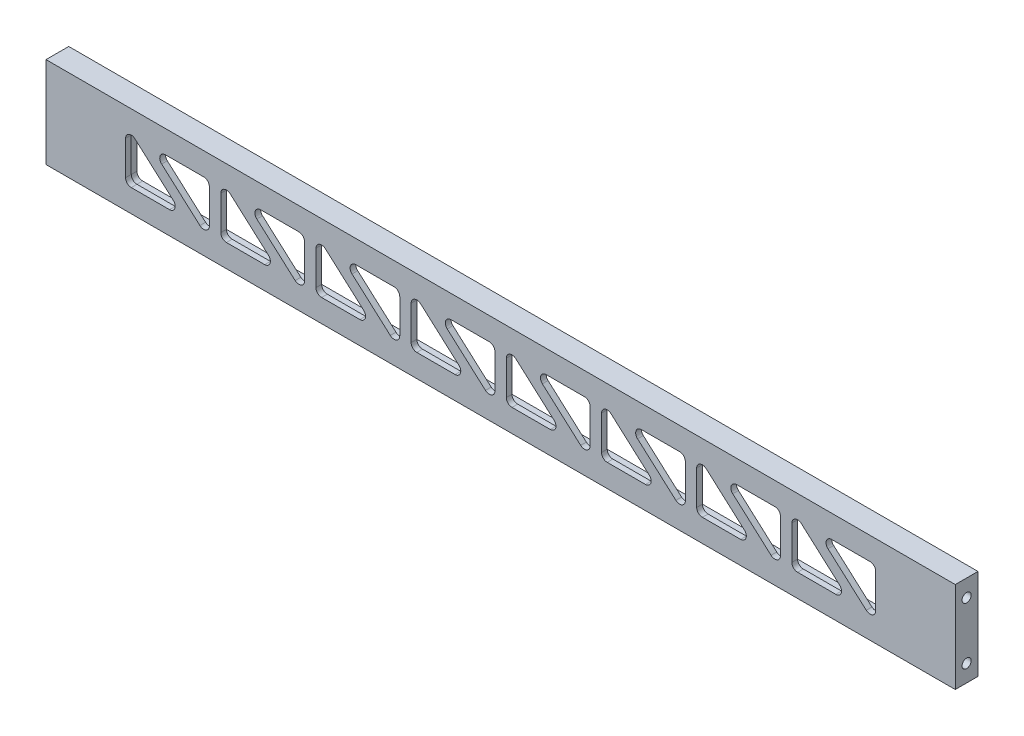
SolidWorks part; units mm, degrees
material "6061 Alloy"
ref_plane "Front Plane" through (0, 0, 0) normal (0, 0, 1) x (1, 0, 0)
ref_plane "Top Plane" through (0, 0, 0) normal (0, 1, 0) x (1, 0, 0)
ref_plane "Right Plane" through (0, 0, 0) normal (1, 0, 0) x (0, 0, -1)
sketch "Sketch1" plane through (0, 0, 0) normal (1, 0, 0) x (0, 0, -1)
  line L1 (0, 0) -> (12.7, 0)
  line L2 (0, 0) -> (0, 50.8)
  line L3 (0, 50.8) -> (12.7, 50.8)
  line L4 (12.7, 0) -> (12.7, 50.8)
  dimension "D1" = 12.7
  dimension "D2" = 50.8
extrude "Boss-Extrude1" add sketch "Sketch1" along normal mid plane 508
hole_wizard "1/4-20 Tapped Hole1" positions "3DSketch1" profile "Sketch2" tap size "1/4-20" standard "ANSI Inch"
sketch3d "3DSketch1"
  line L2 (254, 9.525, -6.35) -> (254, 41.275, -6.35) construction
  line L4 (254, 41.275, -6.35) -> (254, 50.8, -6.35) construction
  line L5 (254, 50.8, -12.7) -> (254, 50.8, 0) construction
  line L8 (254, 9.525, -6.35) -> (254, 0, -6.35) construction
  line L9 (254, 0, 0) -> (254, 0, -12.7) construction
  point P0 (254, 41.275, -6.35)
  point P2 (254, 9.525, -6.35)
  point P4 (-254, 9.525, -6.35)
  point P6 (-254, 41.275, -6.35)
  dimension "D1" = 31.75
sketch "Sketch2" plane through (254, 41.275, -6.35) normal (0, 1, 0) x (0, 0, -1)
  line L0 (0, 0) -> (0, 30.7438)
  line L1 (0, 30.7438) -> (2.5527, 29.21)
  line L2 (2.5527, 29.21) -> (2.5527, 0)
  line L5 (2.5527, 0) -> (0, 0)
  line L10 (0, 30.7438) -> (-2.5527, 29.21) construction
  line L11 (0, -6.35) -> (0, 107.95) construction
  dimension "Tap Drill Dia." = 5.1054
  dimension "Tap Drill Depth" = 29.21
  dimension "Drill Angle" = 118
sketch "Sketch4" plane through (0, 0, -12.7) normal (0, 0, -1) x (-1, 0, 0)
  line L0 (0, 0) -> (0, 6.35) construction
  line L1 (212.725, 44.45) -> (-212.725, 44.45)
  line L2 (215.9, 41.275) -> (215.9, 9.525)
  line L3 (212.725, 6.35) -> (-212.725, 6.35)
  line L4 (-215.9, 41.275) -> (-215.9, 9.525)
  line L5 (-254, 0) -> (254, 0) construction
  line L6 (0, 44.45) -> (0, 50.8) construction
  line L7 (-254, 50.8) -> (254, 50.8) construction
  line L8 (254, 25.4) -> (215.9, 25.4) construction
  line L9 (254, 0) -> (254, 50.8) construction
  line L10 (-254, 25.4) -> (-215.9, 25.4) construction
  line L11 (-254, 0) -> (-254, 50.8) construction
  arc A0 (-212.725, 6.35) -> (-215.9, 9.525) centre (-212.725, 9.525) cw
  arc A1 (-212.725, 44.45) -> (-215.9, 41.275) centre (-212.725, 41.275) ccw
  arc A2 (215.9, 9.525) -> (212.725, 6.35) centre (212.725, 9.525) cw
  arc A3 (212.725, 44.45) -> (215.9, 41.275) centre (212.725, 41.275) cw
  dimension "D1" = 3.175
  dimension "D2" = 6.35
  dimension "D3" = 38.1
extrude "Cut-Extrude1" cut sketch "Sketch4" against normal blind 9.525
sketch "Sketch5" plane through (0, 0, -3.175) normal (0, 0, -1) x (-1, 0, 0)
  line L0 (-209.55, 34.925) -> (-209.55, 15.875)
  line L1 (-204.2632, 13.5041) -> (-182.876, 32.5541)
  line L2 (-184.9878, 38.1) -> (-206.375, 38.1)
  line L3 (-189.3927, 18.2459) -> (-168.0055, 37.2959)
  line L4 (-162.7188, 34.925) -> (-162.7188, 15.875)
  line L5 (-165.8937, 12.7) -> (-187.2809, 12.7)
  line L6 (212.725, 44.45) -> (-212.725, 44.45) construction
  line L7 (-212.725, 6.35) -> (212.725, 6.35) construction
  line L8 (-215.9, 25.4) -> (-209.55, 25.4) construction
  line L9 (-215.9, 41.275) -> (-215.9, 9.525) construction
  line L10 (-193.5696, 23.0291) -> (-189.3461, 18.2874) construction
  line L11 (-162.7187, 25.4) -> (-156.3687, 25.4) construction
  line L12 (-156.3687, 34.925) -> (-156.3687, 15.875)
  line L13 (-131.8066, 38.1) -> (-153.1937, 38.1)
  line L14 (-151.082, 13.5041) -> (-129.6948, 32.5541)
  line L15 (-140.3884, 23.0291) -> (-136.1648, 18.2874) construction
  line L16 (-136.2115, 18.2459) -> (-114.8243, 37.2959)
  line L17 (-109.5375, 34.925) -> (-109.5375, 15.875)
  line L18 (-112.7125, 12.7) -> (-134.0997, 12.7)
  line L19 (-109.5375, 25.4) -> (-103.1875, 25.4) construction
  line L20 (-103.1875, 34.925) -> (-103.1875, 15.875)
  line L21 (-78.6253, 38.1) -> (-100.0125, 38.1)
  line L22 (-97.9007, 13.5041) -> (-76.5135, 32.5541)
  line L23 (-87.2071, 23.0291) -> (-82.9836, 18.2874) construction
  line L24 (-83.0302, 18.2459) -> (-61.643, 37.2959)
  line L25 (-56.3563, 34.925) -> (-56.3563, 15.875)
  line L26 (-59.5313, 12.7) -> (-80.9184, 12.7)
  line L27 (-56.3562, 25.4) -> (-50.0062, 25.4) construction
  line L28 (-50.0063, 34.925) -> (-50.0063, 15.875)
  line L29 (-25.4441, 38.1) -> (-46.8313, 38.1)
  line L30 (-44.7195, 13.5041) -> (-23.3323, 32.5541)
  line L31 (-34.0259, 23.0291) -> (-29.8023, 18.2874) construction
  line L32 (-29.849, 18.2459) -> (-8.4618, 37.2959)
  line L33 (-3.175, 34.925) -> (-3.175, 15.875)
  line L34 (-6.35, 12.7) -> (-27.7372, 12.7)
  line L35 (-3.175, 25.4) -> (3.175, 25.4) construction
  line L36 (3.175, 34.925) -> (3.175, 15.875)
  line L37 (27.7372, 38.1) -> (6.35, 38.1)
  line L38 (8.4618, 13.5041) -> (29.849, 32.5541)
  line L39 (19.1554, 23.0291) -> (23.3789, 18.2874) construction
  line L40 (23.3323, 18.2459) -> (44.7195, 37.2959)
  line L41 (50.0062, 34.925) -> (50.0062, 15.875)
  line L42 (46.8312, 12.7) -> (25.4441, 12.7)
  line L43 (50.0062, 25.4) -> (56.3562, 25.4) construction
  line L44 (56.3562, 34.925) -> (56.3562, 15.875)
  line L45 (80.9184, 38.1) -> (59.5312, 38.1)
  line L46 (61.643, 13.5041) -> (83.0302, 32.5541)
  line L47 (72.3366, 23.0291) -> (76.5602, 18.2874) construction
  line L48 (76.5135, 18.2459) -> (97.9007, 37.2959)
  line L49 (103.1875, 34.925) -> (103.1875, 15.875)
  line L50 (100.0125, 12.7) -> (78.6253, 12.7)
  line L51 (103.1875, 25.4) -> (109.5375, 25.4) construction
  line L52 (109.5375, 34.925) -> (109.5375, 15.875)
  line L53 (134.0997, 38.1) -> (112.7125, 38.1)
  line L54 (114.8243, 13.5041) -> (136.2115, 32.5541)
  line L55 (125.5179, 23.0291) -> (129.7414, 18.2874) construction
  line L56 (129.6948, 18.2459) -> (151.082, 37.2959)
  line L57 (156.3687, 34.925) -> (156.3687, 15.875)
  line L58 (153.1937, 12.7) -> (131.8066, 12.7)
  line L59 (156.3687, 25.4) -> (162.7188, 25.4) construction
  line L60 (162.7187, 34.925) -> (162.7187, 15.875)
  line L61 (187.2809, 38.1) -> (165.8937, 38.1)
  line L62 (168.0055, 13.5041) -> (189.3927, 32.5541)
  line L63 (178.6991, 23.0291) -> (182.9227, 18.2874) construction
  line L64 (182.876, 18.2459) -> (204.2632, 37.2959)
  line L65 (209.55, 34.925) -> (209.55, 15.875)
  line L66 (206.375, 12.7) -> (184.9878, 12.7)
  line L67 (215.9, 25.4) -> (209.55, 25.4) construction
  line L69 (215.9, 9.525) -> (215.9, 41.275) construction
  arc A0 (-189.3927, 18.2459) -> (-187.2809, 12.7) centre (-187.2809, 15.875) ccw
  arc A1 (-162.7188, 15.875) -> (-165.8937, 12.7) centre (-165.8937, 15.875) cw
  arc A2 (-168.0055, 37.2959) -> (-162.7188, 34.925) centre (-165.8937, 34.925) cw
  arc A3 (-182.876, 32.5541) -> (-184.9878, 38.1) centre (-184.9878, 34.925) ccw
  arc A4 (-209.55, 15.875) -> (-204.2632, 13.5041) centre (-206.375, 15.875) ccw
  arc A5 (-209.55, 34.925) -> (-206.375, 38.1) centre (-206.375, 34.925) cw
  arc A6 (-156.3687, 34.925) -> (-153.1937, 38.1) centre (-153.1937, 34.925) cw
  arc A7 (-129.6948, 32.5541) -> (-131.8066, 38.1) centre (-131.8066, 34.925) ccw
  arc A8 (-156.3687, 15.875) -> (-151.082, 13.5041) centre (-153.1937, 15.875) ccw
  arc A9 (-114.8243, 37.2959) -> (-109.5375, 34.925) centre (-112.7125, 34.925) cw
  arc A10 (-109.5375, 15.875) -> (-112.7125, 12.7) centre (-112.7125, 15.875) cw
  arc A11 (-136.2115, 18.2459) -> (-134.0997, 12.7) centre (-134.0997, 15.875) ccw
  arc A12 (-103.1875, 34.925) -> (-100.0125, 38.1) centre (-100.0125, 34.925) cw
  arc A13 (-76.5135, 32.5541) -> (-78.6253, 38.1) centre (-78.6253, 34.925) ccw
  arc A14 (-103.1875, 15.875) -> (-97.9007, 13.5041) centre (-100.0125, 15.875) ccw
  arc A15 (-61.643, 37.2959) -> (-56.3563, 34.925) centre (-59.5313, 34.925) cw
  arc A16 (-56.3563, 15.875) -> (-59.5313, 12.7) centre (-59.5313, 15.875) cw
  arc A17 (-83.0302, 18.2459) -> (-80.9184, 12.7) centre (-80.9184, 15.875) ccw
  arc A18 (-50.0063, 34.925) -> (-46.8313, 38.1) centre (-46.8313, 34.925) cw
  arc A19 (-23.3323, 32.5541) -> (-25.4441, 38.1) centre (-25.4441, 34.925) ccw
  arc A20 (-50.0063, 15.875) -> (-44.7195, 13.5041) centre (-46.8313, 15.875) ccw
  arc A21 (-8.4618, 37.2959) -> (-3.175, 34.925) centre (-6.35, 34.925) cw
  arc A22 (-3.175, 15.875) -> (-6.35, 12.7) centre (-6.35, 15.875) cw
  arc A23 (-29.849, 18.2459) -> (-27.7372, 12.7) centre (-27.7372, 15.875) ccw
  arc A24 (3.175, 34.925) -> (6.35, 38.1) centre (6.35, 34.925) cw
  arc A25 (29.849, 32.5541) -> (27.7372, 38.1) centre (27.7372, 34.925) ccw
  arc A26 (3.175, 15.875) -> (8.4618, 13.5041) centre (6.35, 15.875) ccw
  arc A27 (44.7195, 37.2959) -> (50.0062, 34.925) centre (46.8312, 34.925) cw
  arc A28 (50.0062, 15.875) -> (46.8312, 12.7) centre (46.8312, 15.875) cw
  arc A29 (23.3323, 18.2459) -> (25.4441, 12.7) centre (25.4441, 15.875) ccw
  arc A30 (56.3562, 34.925) -> (59.5312, 38.1) centre (59.5312, 34.925) cw
  arc A31 (83.0302, 32.5541) -> (80.9184, 38.1) centre (80.9184, 34.925) ccw
  arc A32 (56.3562, 15.875) -> (61.643, 13.5041) centre (59.5312, 15.875) ccw
  arc A33 (97.9007, 37.2959) -> (103.1875, 34.925) centre (100.0125, 34.925) cw
  arc A34 (103.1875, 15.875) -> (100.0125, 12.7) centre (100.0125, 15.875) cw
  arc A35 (76.5135, 18.2459) -> (78.6253, 12.7) centre (78.6253, 15.875) ccw
  arc A36 (109.5375, 34.925) -> (112.7125, 38.1) centre (112.7125, 34.925) cw
  arc A37 (136.2115, 32.5541) -> (134.0997, 38.1) centre (134.0997, 34.925) ccw
  arc A38 (109.5375, 15.875) -> (114.8243, 13.5041) centre (112.7125, 15.875) ccw
  arc A39 (151.082, 37.2959) -> (156.3687, 34.925) centre (153.1937, 34.925) cw
  arc A40 (156.3687, 15.875) -> (153.1937, 12.7) centre (153.1937, 15.875) cw
  arc A41 (129.6948, 18.2459) -> (131.8066, 12.7) centre (131.8066, 15.875) ccw
  arc A42 (162.7187, 34.925) -> (165.8937, 38.1) centre (165.8937, 34.925) cw
  arc A43 (189.3927, 32.5541) -> (187.2809, 38.1) centre (187.2809, 34.925) ccw
  arc A44 (162.7187, 15.875) -> (168.0055, 13.5041) centre (165.8937, 15.875) ccw
  arc A45 (204.2632, 37.2959) -> (209.55, 34.925) centre (206.375, 34.925) cw
  arc A46 (209.55, 15.875) -> (206.375, 12.7) centre (206.375, 15.875) cw
  arc A47 (182.876, 18.2459) -> (184.9878, 12.7) centre (184.9878, 15.875) ccw
  point P18 (-165.8937, 38.1)
  point P19 (-206.375, 12.7)
  dimension "D1" = 3.175
  dimension "D2" = 6.35
  dimension "D3" = 6.35
  dimension "D4" = 6.35
  dimension "D5" = 8
extrude "Cut-Extrude2" cut sketch "Sketch5" against normal through all
